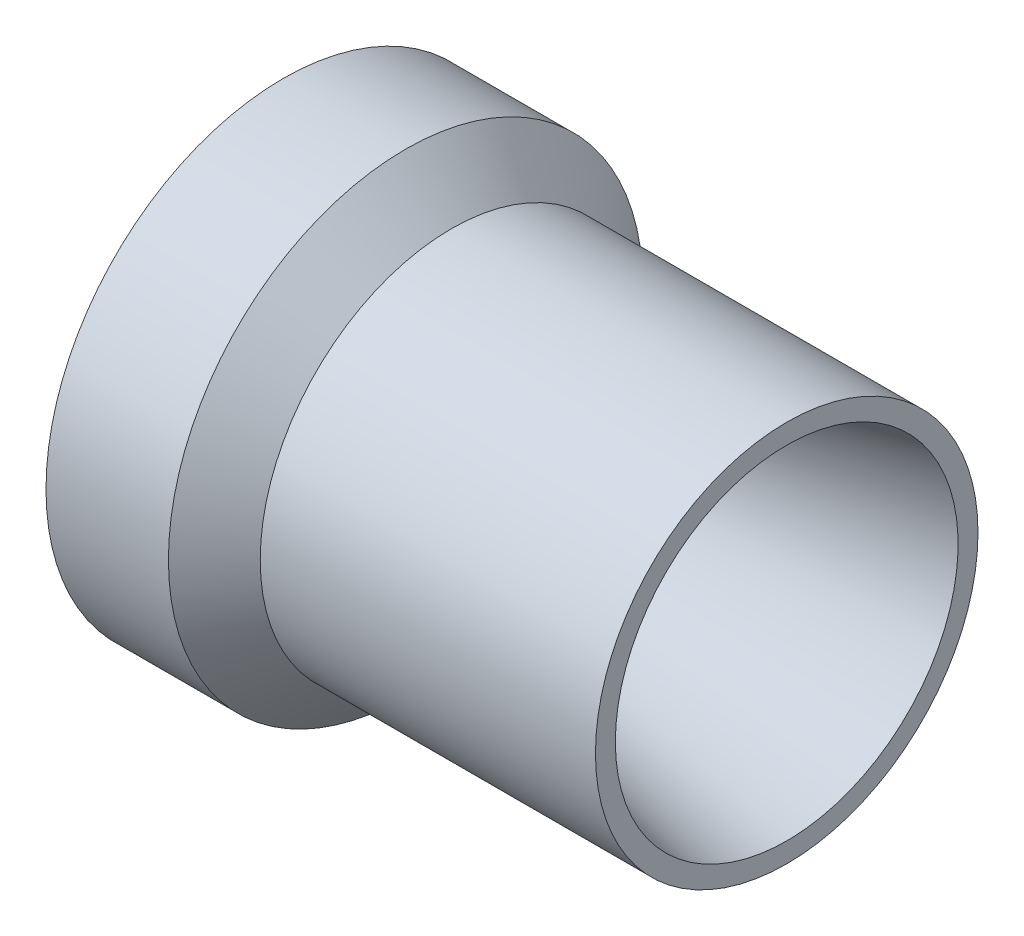
SolidWorks part; units mm, degrees
material "C (Graphite)"
ref_plane "Front Plane" through (0, 0, 0) normal (0, 0, 1) x (1, 0, 0)
ref_plane "Top Plane" through (0, 0, 0) normal (0, 1, 0) x (1, 0, 0)
ref_plane "Right Plane" through (0, 0, 0) normal (1, 0, 0) x (0, 0, -1)
sketch "Sketch1" plane through (0, 0, 0) normal (0, 0, 1) x (1, 0, 0)
  line L0 (0, 0) -> (0, 9.525)
  line L1 (104.4797, 23.1775) -> (20.8314, 40.9575)
  line L2 (0, 9.525) -> (0, 15.875)
  line L3 (0, 58.7375) -> (76.2, 58.7375) construction
  line L5 (14.4814, 40.9575) -> (20.8314, 40.9575)
  line L6 (104.4797, 23.1775) -> (104.4797, 19.05)
  line L7 (25.4, 9.525) -> (0, 9.525)
  line L9 (25.4, 9.525) -> (34.925, 19.05)
  line L12 (34.925, 19.05) -> (104.4797, 19.05)
  line L14 (0, 15.875) -> (14.4814, 40.9575)
  dimension "D1" = 58.7375
  dimension "D2" = 60
  dimension "D3" = 6.35
  dimension "D4" = 25.4
  dimension "D5" = 9.525
  dimension "D6" = 9.525
  dimension "D7" = 12
  dimension "D8" = 135
  dimension "D9" = 17.78
  dimension "D10" = 6.35
  dimension "D11" = 69.5547
  dimension "D12" = 35.56
revolve "Revolve1" add sketch "Sketch1" angle 360 about L3 region at (40.0398, 24.7628, 0)
